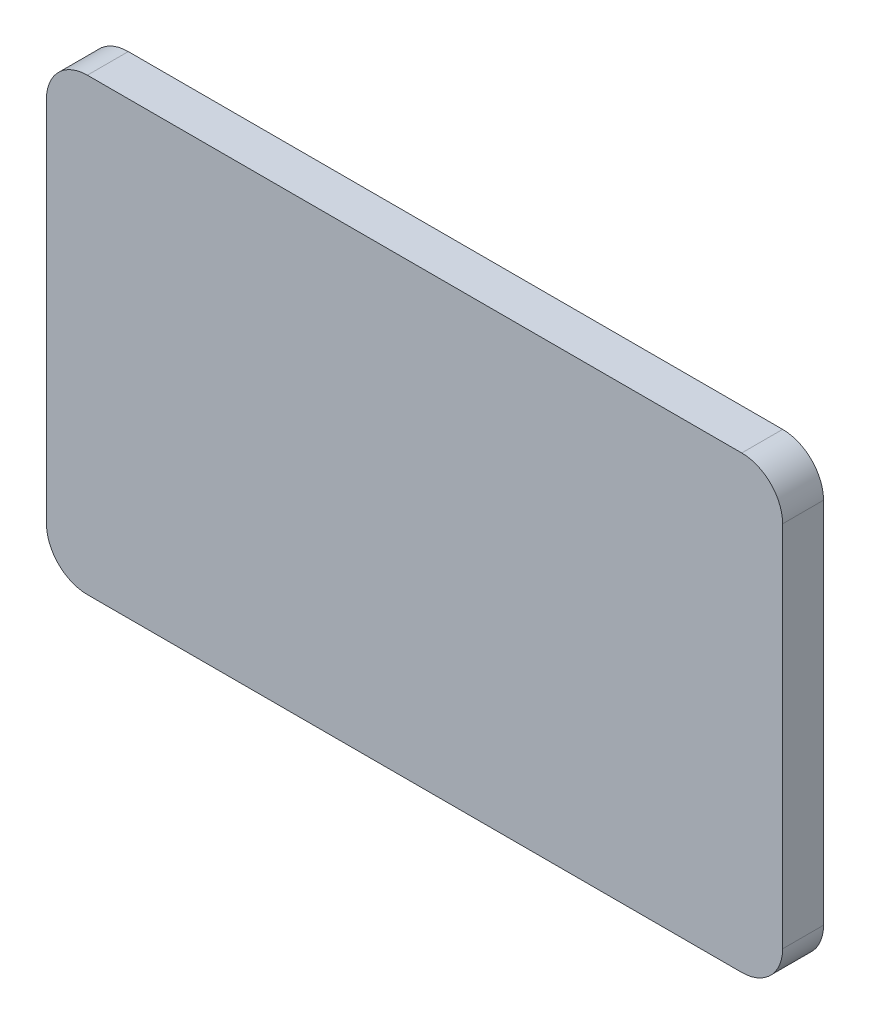
SolidWorks part; units mm, degrees
ref_plane "Front Plane" through (0, 0, 0) normal (0, 0, 1) x (1, 0, 0)
ref_plane "Top Plane" through (0, 0, 0) normal (0, 1, 0) x (1, 0, 0)
ref_plane "Right Plane" through (0, 0, 0) normal (1, 0, 0) x (0, 0, -1)
sketch "Sketch1" plane through (0, 0, 0) normal (0, 0, 1) x (1, 0, 0)
  line L1 (-22.86, -13.97) -> (22.86, -13.97)
  line L2 (-22.86, -13.97) -> (-22.86, 13.97)
  line L3 (-22.86, 13.97) -> (22.86, 13.97)
  line L4 (22.86, -13.97) -> (22.86, 13.97)
  line L5 (-22.86, -13.97) -> (22.86, 13.97) construction
  line L6 (-22.86, 13.97) -> (22.86, -13.97) construction
  point P0 (0, 0)
  dimension "D1" = 45.72
  dimension "D2" = 27.94
extrude "Boss-Extrude1" add sketch "Sketch1" along normal mid plane 2.54
fillet "Fillet1" radius 2.54 4 edges at (22.86, 13.97, 0) (22.86, -13.97, 0) (-22.86, -13.97, 0) (-22.86, 13.97, 0)
